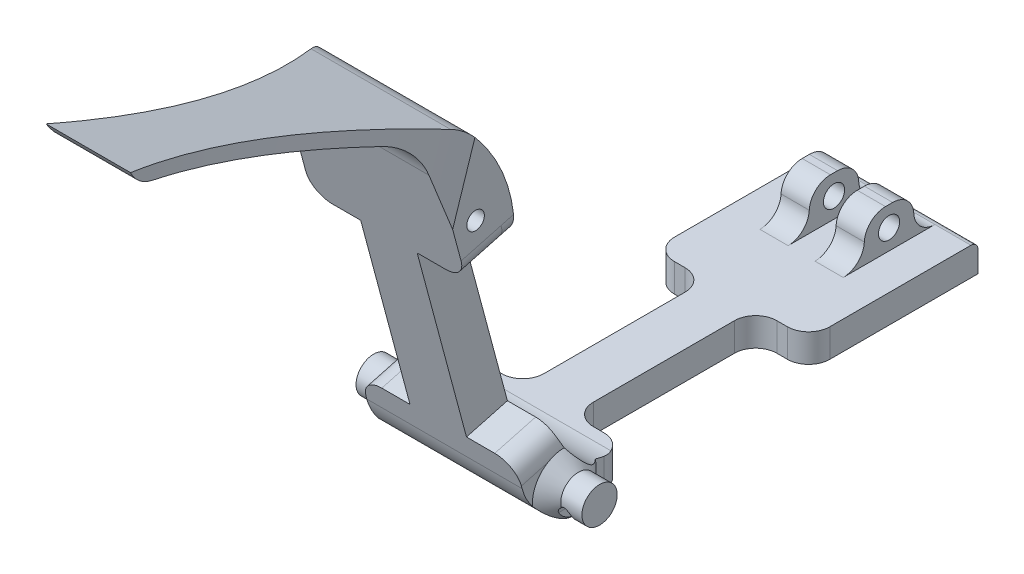
SolidWorks part; units mm, degrees
ref_plane "Front Plane" through (0, 0, 0) normal (0, 0, 1) x (1, 0, 0)
ref_plane "Top Plane" through (0, 0, 0) normal (0, 1, 0) x (1, 0, 0)
ref_plane "Right Plane" through (0, 0, 0) normal (1, 0, 0) x (0, 0, -1)
sketch "Sketch1" plane through (0, 0, 0) normal (1, 0, 0) x (0, 0, -1)
  line L4 (0, 0) -> (63, 0)
  line L5 (63, 0) -> (63, -4)
  line L6 (63, -4) -> (0, -4)
  line L7 (0, -4) -> (0, 0)
  line L12 (0, -4) -> (-14.235, 49.1259)
  line L13 (5.1399, 0) -> (-8.0234, 49.1259)
  line L14 (-14.235, 49.1259) -> (-8.0234, 49.1259)
  dimension "D1" = 63
  dimension "D2" = 4
  dimension "D3" = 15
  dimension "D4" = 55
  dimension "D5" = 6
extrude "Boss-Extrude1" add sketch "Sketch1" along normal blind 22 contours L6 | L6 L4 region at (0, 24.3823, 4.5184) region at (0, -2, -31.5)
sketch "Sketch2" plane through (0, 0, 0) normal (0, 1, 0) x (1, 0, 0)
  line L0 (11, 5.1399) -> (11, 63)
  line L1 (22, 5.1399) -> (0, 5.1399) construction
  line L2 (22, 63) -> (0, 63) construction
  line L3 (16.9, 52) -> (12.9, 52)
  line L4 (5.1, 52) -> (9.1, 52)
  line L5 (5.1, 52) -> (5.1, 59)
  line L6 (5.1, 59) -> (9.1, 59)
  line L7 (9.1, 52) -> (9.1, 59)
  line L8 (16.9, 59) -> (12.9, 59)
  line L9 (12.9, 52) -> (12.9, 59)
  line L10 (16.9, 52) -> (16.9, 59)
  dimension "D1" = 1.9
  dimension "D2" = 7
  dimension "D3" = 4
  dimension "D4" = 4
extrude "Boss-Extrude2" add sketch "Sketch2" along normal blind 5.7 contours L4 L7 L6 L5 | L3 L10 L8 L9 region at (14.9, 0, -55.5) region at (7.1, 0, -55.5)
sketch "Sketch4" plane through (16.9, 0, 0) normal (1, 0, 0) x (0, 0, -1)
  line L0 (52, 5.7) -> (59, 0)
  circle A0 centre (55.5, 2.85) radius 1.5
  dimension "D1" = 3
extrude "Cut-Extrude1" cut sketch "Sketch4" against normal through all contours L0 A0 | L0 A0 region at (16.9, 3.3437, -55.902) region at (16.9, 2.3563, -55.098)
sketch "Sketch5" plane through (22, 0, 0) normal (1, 0, 0) x (0, 0, -1)
  line L0 (-11.1292, 49.1259) -> (-5.1214, 26.7046)
  line L1 (-14.235, 49.1259) -> (-8.0234, 49.1259) construction
  line L2 (5.1399, 0) -> (-8.0234, 49.1259) construction
  circle A0 centre (-8.1825, 38.1287) radius 1.25
  dimension "D1" = 2.5
  dimension "D2" = 10.9972
extrude "Cut-Extrude2" cut sketch "Sketch5" against normal through all contours L0 A0 | L0 A0 region at (22, 38.266, 7.6701) region at (22, 37.9914, 8.695)
sketch "Sketch6" plane through (22, 0, 0) normal (1, 0, 0) x (0, 0, -1)
  line L0 (-14.235, 49.1259) -> (-58.2649, 63.4321)
  line L1 (-8.0234, 49.1259) -> (-30.4404, 49.1259) construction
  line L2 (-8.0234, 49.1259) -> (-52.0532, 63.4321)
  line L3 (-58.2649, 63.4321) -> (-52.0532, 63.4321)
  line L4 (-14.235, 49.1259) -> (-8.0234, 49.1259)
  dimension "D1" = 18
extrude "Boss-Extrude3" add sketch "Sketch6" against normal up to surface (22 mm away) up to face at (0, 38.1287, 6.9325)
fillet "Fillet5" radius 7 1 edges at (11, 63.4321, 58.2649)
fillet "Fillet7" radius 3 4 edges at (14.9, 0, -52) (14.9, 0, -59) (7.1, 0, -59) (7.1, 0, -52)
fillet "Fillet8" radius 3 4 edges at (14.9, 5.7, -52) (14.9, 5.7, -59) (7.1, 5.7, -59) (7.1, 5.7, -52)
sketch "Sketch7" plane through (0, 0, 0) normal (0, 1, 0) x (1, 0, 0)
  line L0 (0, 5.1399) -> (0, 63) construction
  line L1 (0, 39) -> (7.5, 39)
  line L2 (0, 39) -> (0, 13)
  line L3 (0, 13) -> (7.5, 13)
  line L4 (7.5, 39) -> (7.5, 13)
  line L5 (11, 63) -> (11, 5.1399) construction
  line L6 (22, 63) -> (0, 63) construction
  line L7 (22, 5.1399) -> (0, 5.1399) construction
  line L8 (22, 13) -> (14.5, 13)
  line L9 (14.5, 39) -> (14.5, 13)
  line L10 (22, 39) -> (14.5, 39)
  line L11 (22, 39) -> (22, 13)
  dimension "D1" = 24
  dimension "D2" = 26
  dimension "D3" = 3.5
extrude "Cut-Extrude3" cut sketch "Sketch7" against normal through all
sketch "Sketch8" plane through (0, 1.285, -4.7956) normal (0, 0.2588, -0.9659) x (-1, 0, 0)
  line L0 (0, -1.3303) -> (0, 49.5286) construction
  line L1 (0, 32.6697) -> (-7, 32.6697)
  line L2 (0, 32.6697) -> (0, 5.6697)
  line L3 (0, 5.6697) -> (-7, 5.6697)
  line L4 (-7, 32.6697) -> (-7, 5.6697)
  line L5 (-11, -1.3303) -> (-11, 49.5286)
  line L6 (-22, -1.3303) -> (0, -1.3303) construction
  line L7 (-22, 49.5286) -> (0, 49.5286) construction
  line L8 (-22, 5.6697) -> (-15, 5.6697)
  line L9 (-15, 32.6697) -> (-15, 5.6697)
  line L10 (-22, 32.6697) -> (-15, 32.6697)
  line L11 (-22, 32.6697) -> (-22, 5.6697)
  line L13 (-5, 36.6697) -> (-17, 36.6697)
  line L14 (-5, 36.6697) -> (-5, 43.5286)
  line L15 (-5, 43.5286) -> (-17, 43.5286)
  line L16 (-17, 36.6697) -> (-17, 43.5286)
  point P20 (-11, 43.5286)
  line M6 (0, -1.3303) -> (0, 49.5286)
  line M8 (-22, 49.5286) -> (-22, -1.3303)
  dimension "D1" = 27
  dimension "D2" = 7
  dimension "D3" = 7
  dimension "D4" = 12
  dimension "D5" = 4
  dimension "D6" = 6
extrude "Cut-Extrude5" cut sketch "Sketch8" against normal through all and the other way through all contours L10 L8 L9 M8 | L1 L4 L3 M6 region at (3.5, 19.8015, 0.1659) region at (18.5, 19.8015, 0.1659)
sketch "Sketch9" plane through (0, 42.0768, -13.6716) normal (0, 0.9511, -0.309) x (1, 0, 0)
  line L0 (0, -69.1072) -> (22, -69.1072) construction
  line L1 (11, -69.1072) -> (11, -22.8114)
  line L2 (22, -22.8114) -> (0, -22.8114) construction
  line L3 (0, -22.8114) -> (0, -69.1072)
  line L4 (0, -69.1072) -> (5.0133, -69.1072)
  line L5 (22, -22.8114) -> (22, -69.1072)
  line L6 (22, -69.1072) -> (16.9867, -69.1072)
  spline S0 degree 2 poles (22, -22.8114) (12.328, -45.3336) (16.9867, -69.1072) knots 0 0 0 1 1 1
  spline S1 degree 2 poles (0, -22.8114) (9.672, -45.3336) (5.0133, -69.1072) knots 0 0 0 1 1 1
  line M2 (0, -22.8114) -> (0, -69.1072)
  line M3 (0, -69.1072) -> (22, -69.1072)
  line M4 (22, -69.1072) -> (22, -22.8114)
extrude "Cut-Extrude6" cut sketch "Sketch9" against normal through all contours S1 M2 M3 | S0 M4 M3 region at (2.7833, 57.4754, 33.7204) region at (19.2167, 57.4754, 33.7204)
fillet "Fillet12" radius 8 1 edges at (11, 0, -5.1399)
fillet "Fillet13" radius 8 1 edges at (11, -4, 0)
fillet "Fillet14" radius 3 8 edges at (0, -2, -13) (7.5, -2, -13) (7.5, -2, -39) (0, -2, -39) (22, -2, -13) (14.5, -2, -13) (14.5, -2, -39) (22, -2, -39)
fillet "Fillet15" radius 3 8 edges at (22, 32.065, 6.5578) (15, 32.065, 6.5578) (15, 5.985, -0.4303) (22, 5.985, -0.4303) (0, 32.065, 6.5578) (7, 32.065, 6.5578) (7, 5.985, -0.4303) (0, 5.985, -0.4303)
fillet "Fillet17" radius 5 1 edges at (11, 49.1259, 8.0234)
fillet "Fillet18" radius 7 1 edges at (11, 49.1259, 14.235)
fillet "Fillet19" radius 1 1 edges at (11, 0, -63)
ref_plane "Plane2" through (11, 0, 0) normal (-1, 0, 0) x (0, 0, 1)
sketch "Sketch13" plane through (22, 0, 0) normal (1, 0, 0) x (0, 0, -1)
  line L0 (-1.691, 2.3108) -> (10, 0.1028)
  line L1 (4.3858, 3.9391) -> (4.3858, -3.8056)
  arc A0 (-1.5888, 1.9294) -> (6.1386, -4) centre (6.1386, 4) ccw construction
  circle A1 centre (4.3858, -0.5389) radius 2.5
  dimension "D1" = 5
extrude "Boss-Extrude5" add sketch "Sketch13" along normal blind 5 contours L1 A1 | L1 A1 | L0 A1 L1 | L1 A1 L0 region at (22, 1.5681, -3.8297) region at (22, -0.7121, -3.2833) region at (22, 1.3631, -5.259) region at (22, -0.851, -5.4777)
ref_plane "Plane3" through (0, 0, -6.8858) normal (0, 0, -1) x (-1, 0, 0)
sketch "Sketch14" plane through (0, 0, -6.8858) normal (0, 0, -1) x (-1, 0, 0)
  line L0 (-27, -3.0389) -> (-22, -3.0389) construction
  line L1 (-25.2513, -3.0389) -> (-23.6707, -3.0389)
  line L2 (-25.2513, -3.0389) -> (-25.2513, -0.9192)
  line L3 (-25.2513, -0.9192) -> (-23.6707, -0.9192)
  line L4 (-23.6707, -3.0389) -> (-23.6707, -0.9192)
extrude "Cut-Extrude8" cut sketch "Sketch14" against normal through all
mirror "Mirror2" about plane through (11, 0, 0) normal (-1, 0, 0) of "Cut-Extrude8", "Boss-Extrude5"
fillet "Fillet23" radius 2 2 edges at (22, -0.5389, -6.8858) (0, -0.5389, -6.8858) profile chamfer
fillet "Fillet24" radius 1 4 edges at (25.2513, -0.9192, -4.3858) (23.6707, -0.9192, -4.3858) (-1.6707, -0.9192, -4.3858) (-3.2513, -0.9192, -4.3858)
ref_plane "Plane4" through (11, 0, 0) normal (1, 0, 0) x (0, 0, -1)
sketch "Sketch15" plane through (11, 0, 0) normal (1, 0, 0) x (0, 0, -1)
  line L0 (-8.271, 48.3639) -> (-2.8835, 29.9437)
  spline S0 degree 2 poles (-2.8835, 29.9437) (-1.4618, 40.3362) (-8.271, 48.3639) knots 0 0 0 1 1 1
extrude "Boss-Extrude6" add sketch "Sketch15" along normal up to surface and the other way up to surface up to face at (22, -1.9339, -9.164) other way up to face at (0, 38.1287, 6.9325)
extrude "Cut-Extrude9" cut sketch "Sketch8<4>" along normal through all and the other way blind 10 contours L10 L8 L9 M8 | L1 L4 L3 M6 region at (3.5, 19.8015, 0.1659) region at (18.5, 19.8015, 0.1659)
sketch "Sketch8<4>" plane through (0, 1.285, -4.7956) normal (0, 0.2588, -0.9659) x (-1, 0, 0) same geometry as "Sketch8"
fillet "Fillet25" radius 3 2 edges at (0, 32.9692, 3.1832) (22, 32.9692, 3.1832)
